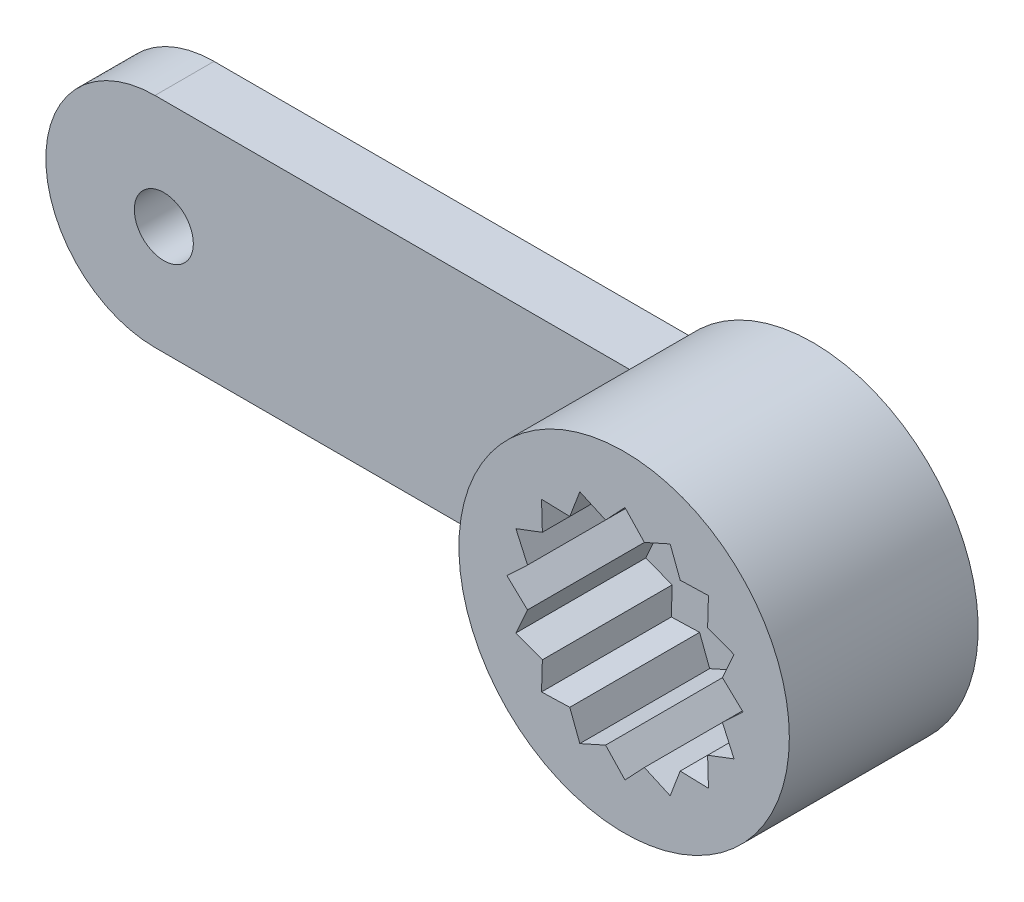
SolidWorks part; units mm, degrees
ref_plane "Front Plane" through (0, 0, 0) normal (0, 0, 1) x (1, 0, 0)
ref_plane "Top Plane" through (0, 0, 0) normal (0, 1, 0) x (1, 0, 0)
ref_plane "Right Plane" through (0, 0, 0) normal (1, 0, 0) x (0, 0, -1)
sketch "Sketch1" plane through (0, 0, 0) normal (0, 0, 1) x (1, 0, 0)
  circle A0 centre (0, 0) radius 2.8
  dimension "D1" = 5.6
extrude "Boss-Extrude1" add sketch "Sketch1" along normal blind 3.2
sketch "Sketch2" plane through (0, 0, 3.2) normal (0, 0, 1) x (1, 0, 0)
  line L0 (0.0147, -0.0147) -> (0.0147, 1.9853) construction
  line L1 (0.0147, -0.0147) -> (0.3432, 1.637) construction
  line L2 (0.0147, -0.0147) -> (-0.3139, 1.637) construction
  line L3 (0.0147, 1.9853) -> (-0.3139, 1.637)
  line L4 (0.0147, 1.9853) -> (0.3432, 1.637)
  line L5 (0.78, 1.8331) -> (0.9502, 1.3855)
  line L6 (0.78, 1.8331) -> (0.3432, 1.637)
  line L7 (1.4289, 1.3996) -> (1.4148, 0.9209)
  line L8 (1.4289, 1.3996) -> (0.9502, 1.3855)
  line L9 (1.8624, 0.7507) -> (1.6663, 0.3139)
  line L10 (1.8624, 0.7507) -> (1.4148, 0.9209)
  line L11 (2.0147, -0.0147) -> (1.6663, -0.3432)
  line L12 (2.0147, -0.0147) -> (1.6663, 0.3139)
  line L13 (1.8624, -0.78) -> (1.4148, -0.9502)
  line L14 (1.8624, -0.78) -> (1.6663, -0.3432)
  line L15 (1.4289, -1.4289) -> (0.9502, -1.4148)
  line L16 (1.4289, -1.4289) -> (1.4148, -0.9502)
  line L17 (0.78, -1.8624) -> (0.3432, -1.6663)
  line L18 (0.78, -1.8624) -> (0.9502, -1.4148)
  line L19 (0.0147, -2.0147) -> (-0.3139, -1.6663)
  line L20 (0.0147, -2.0147) -> (0.3432, -1.6663)
  line L21 (-0.7507, -1.8624) -> (-0.9209, -1.4148)
  line L22 (-0.7507, -1.8624) -> (-0.3139, -1.6663)
  line L23 (-1.3996, -1.4289) -> (-1.3855, -0.9502)
  line L24 (-1.3996, -1.4289) -> (-0.9209, -1.4148)
  line L25 (-1.8331, -0.78) -> (-1.637, -0.3432)
  line L26 (-1.8331, -0.78) -> (-1.3855, -0.9502)
  line L27 (-1.9853, -0.0147) -> (-1.637, 0.3139)
  line L28 (-1.9853, -0.0147) -> (-1.637, -0.3432)
  line L29 (-1.8331, 0.7507) -> (-1.3855, 0.9209)
  line L30 (-1.8331, 0.7507) -> (-1.637, 0.3139)
  line L31 (-1.3996, 1.3996) -> (-0.9209, 1.3855)
  line L32 (-1.3996, 1.3996) -> (-1.3855, 0.9209)
  line L33 (-0.7507, 1.8331) -> (-0.3139, 1.637)
  line L34 (-0.7507, 1.8331) -> (-0.9209, 1.3855)
extrude "Cut-Extrude1" cut sketch "Sketch2" against normal blind 2.2
sketch "Sketch3" plane through (0, 0, 0) normal (0, 0, 1) x (1, 0, 0)
  circle A1 centre (0, 0) radius 0.75
  dimension "D1" = 1.5
extrude "Cut-Extrude2" cut sketch "Sketch3" along normal blind 1
sketch "Sketch4" plane through (0, 0, 0) normal (0, 0, 1) x (1, 0, 0)
  line L0 (0, -2.8) -> (0, 2.8) construction
  line L1 (10.15, 1.85) -> (-10.15, 1.85) construction
  line L2 (10.15, -1.85) -> (-10.15, -1.85) construction
  line L3 (-10.15, 1.85) -> (-10.15, -1.85) construction
  line L4 (-0.75, 1.85) -> (-0.75, -1.85)
  line L5 (0, -1.85) -> (-0.0802, -1.9054)
  line L6 (0.75, 0) -> (-0.75, 0) construction
  line L7 (-0.75, 1.85) -> (-10.15, 1.85)
  line L8 (-10.15, -1.85) -> (-0.75, -1.85)
  circle A0 centre (0, 0) radius 2.8 construction
  arc A1 (-10.15, 1.85) -> (-10.15, -1.85) centre (-10.15, 0) ccw
  circle A2 centre (0, 0) radius 0.75 construction
  point P5 (0, 0)
  point P19 (0, 0)
  point P21 (0, 1.85)
  point P22 (0, 0)
  dimension "D1" = 3.7
  dimension "D3" = 10.15
extrude "Boss-Extrude2" add sketch "Sketch4" along normal blind 1 contours L7 A1 L8 L4
sketch "Sketch5" plane through (0, 0, 0) normal (0, 0, -1) x (-1, 0, 0)
  line L0 (0, 0) -> (14.3906, 0) construction
  line L1 (0, -5.9427) -> (0, 5.9427) construction
  circle A0 centre (10, 0) radius 0.5
  dimension "D1" = 10
extrude "Cut-Extrude3" cut sketch "Sketch5" against normal up to next
